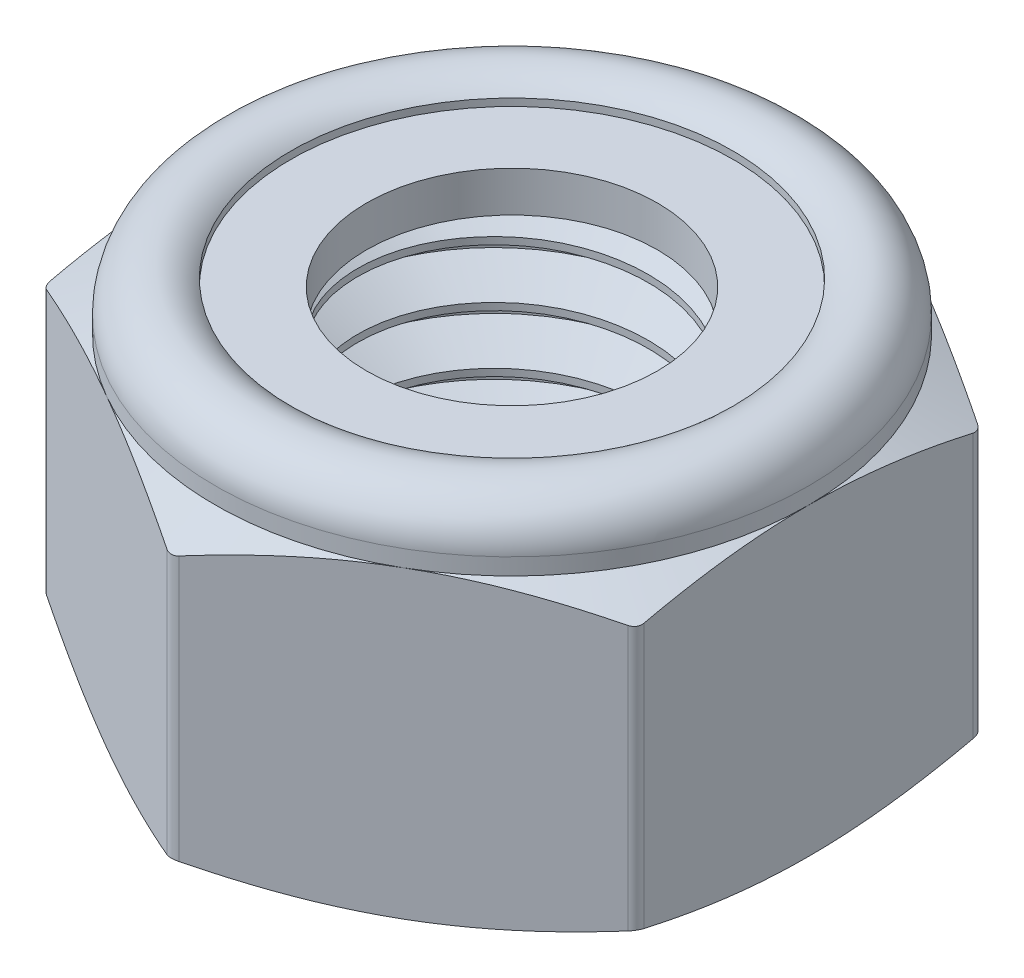
SolidWorks part; units mm, degrees
note: '?' marks a value the reader was unsure of.
material "Plain Carbon Steel"
ref_plane "Front Plane" through (0, 0, 0) normal (0, 0, 1) x (1, 0, 0)
ref_plane "Top Plane" through (0, 0, 0) normal (0, 1, 0) x (1, 0, 0)
ref_plane "Right Plane" through (0, 0, 0) normal (1, 0, 0) x (0, 0, -1)
sketch "Sketch1" plane through (0, 0, 0) normal (0, 0, 1) x (1, 0, 0)
  line L0 (0, -4) -> (0, 4) construction
  line L1 (6.5, 0) -> (-6.5, 0) construction
  line L2 (4, -4) -> (-4, -4) construction
  line L3 (4, -4) -> (4, -2.75) construction
  point P4 (0, 0)
  point P8 (0, 0)
  point P11 (0, -4)
  dimension "Height" = 8
  dimension "Width" = 13
  dimension "Thread Size" = 8
  dimension "Thread Pitch" = 1.25
sketch "Sketch2" plane through (0, 0, 0) normal (0, 1, 0) x (1, 0, 0)
  line L0 (-4, 0.5469) -> (-4, -0.5469) construction
  line L1 (0, 7.5056) -> (-6.5, 3.7528)
  line L2 (-6.5, 3.7528) -> (-6.5, -3.7528)
  line L3 (-6.5, -3.7528) -> (0, -7.5056)
  line L4 (0, -7.5056) -> (6.5, -3.7528)
  line L5 (6.5, -3.7528) -> (6.5, 3.7528)
  line L6 (6.5, 3.7528) -> (0, 7.5056)
  line L7 (-4, -0.5469) -> (-3.1881, -0.0781) construction
  line L8 (-3.1881, -0.0781) -> (-3.1881, 0.0781) construction
  line L9 (-3.1881, 0.0781) -> (-4, 0.5469) construction
  line L10 (-3.1881, 0) -> (-4, 0) construction
  line L11 (-3.5941, 0.3125) -> (-3.5941, -0.3125) construction
  line L12 (4, 0) -> (-4, 0) construction
  line L13 (6.5, 0) -> (-6.5, 0) construction
  circle A0 centre (0, 0) radius 6.5 construction
  circle A1 centre (0, 0) radius 3.1881
  point P19 (0, -3.1881)
  dimension "D1" = 0.1562
  dimension "D2" = 0.625
  dimension "D3" = 60
extrude "Boss-Extrude1" add sketch "Sketch2" along normal up to vertex (4 mm away) and the other way up to vertex (4 mm away) up to point (0, 4, 0) other way up to point (0, -4, 0)
fillet "Fillet1" radius 0.26 6 edges at (-6.5, 0, -3.7528) (0, 0, -7.5056) (-6.5, 0, 3.7528) (6.5, 0, -3.7528) (6.5, 0, 3.7528) (0, 0, 7.5056)
sketch "Sketch3" plane through (0, 0, 0) normal (1, 0, 0) x (0, 0, -1)
  line L0 (7.5056, 2.6667) -> (7.5056, 5)
  line L2 (6.5, -4) -> (7.5056, -3.5311)
  line L3 (3.8278, -4) -> (7.4305, -4) construction
  line L4 (7.5056, 4) -> (7.5056, -4) construction
  line L5 (7.5056, -3.5311) -> (7.5056, -4)
  line L6 (7.5056, -4) -> (6.5, -4)
  line L7 (6.5, 2.6667) -> (7.5056, 2.1978)
  line L8 (7.5056, 2.1978) -> (7.5056, 2.6667)
  line L11 (6.5, 2.6667) -> (6.5, 3.03)
  line L12 (3.8278, 4) -> (7.4305, 4) construction
  line L13 (3.1881, 2.6667) -> (4.8441, 2.6667)
  line L14 (4.8441, 2.6667) -> (4.8441, 3.7159)
  line L15 (4.8441, 2.6667) -> (6.5, 2.6667) construction
  line L16 (4.8441, 3.7159) -> (5.53, 3.03) construction
  line L17 (5.53, 3.03) -> (5.53, 4) construction
  line L18 (3.1881, 2.6667) -> (3.1881, 5)
  line L19 (3.1881, 5) -> (7.5056, 5)
  line L21 (3.1881, -4) -> (3.1881, -3.2)
  line L22 (-3.6027, -4) -> (3.6027, -4) construction
  line L24 (3.9881, -4) -> (3.1881, -4)
  line L25 (3.1881, -3.2) -> (3.9881, -4)
  arc A0 (6.5, 3.03) -> (4.8441, 3.7159) centre (5.53, 3.03) ccw
  point P0 (6.5, 2.6667)
  point P1 (6.5, 0)
  point P14 (3.1881, 0)
  dimension "D1" = 6.6667
  dimension "D2" = 25
  dimension "D3" = 45
  dimension "D4" = 1
  dimension "D5" = 0.8
revolve "Cut-Revolve2" cut sketch "Sketch3" angle 360 about L0
sketch "Sketch4" plane through (0, 0, 0) normal (1, 0, 0) x (0, 0, -1)
  line L0 (-4.8441, 3.7159) -> (-4.8441, 2.6667) construction
  line L1 (-3.1881, 2.6667) -> (-4.8441, 2.6667)
  line L2 (-3.1881, 2.6667) -> (-3.1881, 3.5559)
  line L3 (-3.1881, 3.5559) -> (-4.8441, 3.5559)
  line L4 (-4.8441, 2.6667) -> (-4.8441, 3.5559)
  line L5 (4.8441, 3.7159) -> (-4.8441, 3.7159) construction
  line L6 (3.1881, 2.6667) -> (-3.1881, 2.6667) construction
  dimension "D1" = 0.16
revolve "Revolve1" add sketch "Sketch4" angle 360 about L0
sketch "Sketch5" plane through (0, 0, 0) normal (0, 1, 0) x (1, 0, 0)
  circle A0 centre (0, 0) radius 3.1881 construction
  point P0 (0, -3.1881)
sketch "Sketch6" plane through (0, 0, 0) normal (0, 0, 1) x (1, 0, 0)
  line L0 (4, 2.6667) -> (4, -4)
  line L2 (0, -4) -> (6.5, -4) construction
  line L3 (4, -4) -> (0, -4)
  line L4 (0, -4) -> (0, 2.6667)
  line L5 (0, -4) -> (0, 4) construction
  line L6 (0, 2.6667) -> (4, 2.6667)
  line L7 (6.5, 2.6667) -> (3.25, 2.6667) construction
revolve "Revolve2" add sketch "Sketch6" angle 360 about L4
sketch "Sketch7" plane through (0, -4, 0) normal (0, -1, 0) x (1, 0, 0)
  circle A2 centre (0, 0) radius 4
  circle A3 centre (0, 0) radius 4
  dimension "D1" = 0
curve "Helix/Spiral1" pitch 1.25 height 8 turns 6.4
sketch "Sketch8" plane through (0, 0, 0) normal (0, 0, 1) x (1, 0, 0)
  line L0 (4.1353, -3.9219) -> (3.0528, -4.5469) construction
  line L1 (3.0528, -4.5469) -> (4.1353, -5.1719) construction
  line L2 (4.1353, -5.1719) -> (4.1353, -3.9219) construction
  line L3 (3.1881, -4.4687) -> (3.1881, -4.625)
  line L4 (4, -4) -> (4, -5.0937) construction
  line L5 (4, -4.5469) -> (4.1353, -4.5469) construction
  line L6 (3.0528, -4.5469) -> (3.1881, -4.5469) construction
  line L7 (4.0677, -4.5469) -> (4.0677, -5.1328) construction
  line L8 (3.1881, -4.4687) -> (4.1353, -3.9219)
  line L9 (4.1353, -3.9219) -> (4.0677, -5.1328)
  line L10 (3.1881, -4.625) -> (4.0677, -5.1328)
  dimension "D1" = 1.25
  dimension "D2" = 0.1562
sweep "Cut-Sweep1" cut profiles "Sketch8" path "Helix/Spiral1" align with end faces yes
sketch "Sketch9" plane through (0, 0, 0) normal (0, 0, 1) x (1, 0, 0)
  line L0 (0, 0) -> (0, -4)
  line L1 (0, 0) -> (0, 0.8)
  line L2 (0, -4) -> (4, -4)
  line L3 (4, -4) -> (4.8, -4)
  line L4 (4.8, -4) -> (0, 0.8)
  dimension "D1" = 0.8
revolve "Revolve3" add sketch "Sketch9" angle 360 about L0
sketch "Sketch10" plane through (0, -4, 0) normal (0, -1, 0) x (1, 0, 0)
  circle A0 centre (0, 0) radius 3.9881 construction
  circle A1 centre (0, 0) radius 3.9881
extrude "Boss-Extrude2" add sketch "Sketch10" against normal up to surface (6.6667 mm away) up to face at (4.8441, 2.6667, 0)
combine bodies "Combine1" operation type subtract main body 110 bodies to subtract 109
ref_axis "Axis1" through (0, -4.4, 0) along (0, 1, 0)?
equation "\"D1@Sketch3\"=\"Height@sketch1\"*(5/6)"
equation "\"D5@Sketch3\"=\"Thread Size@Sketch1\"*.1"
equation "\"D4@Helix/Spiral1\"=\"Thread Pitch@sketch1\""
equation "\"D3@Helix/Spiral1\"=\"Height@sketch1\""
equation "\"D1@Sketch8\"=\"Thread Pitch@sketch1\""
equation "\"D2@Sketch8\"=\"Thread Pitch@sketch1\"/8"
equation "\"D1@Sketch9\"=\"Thread Size@Sketch1\" * .1"
equation "\"D1@Sketch2\"=\"Thread Pitch@sketch1\"/8"
equation "\"D2@Sketch2\"=\"Thread Pitch@sketch1\"/2"
equation "\"D1@Sketch4\" = \"Height@Sketch1\" * .02"
equation "\"D1@Fillet1\"=\"Width@sketch1\"*.02"
